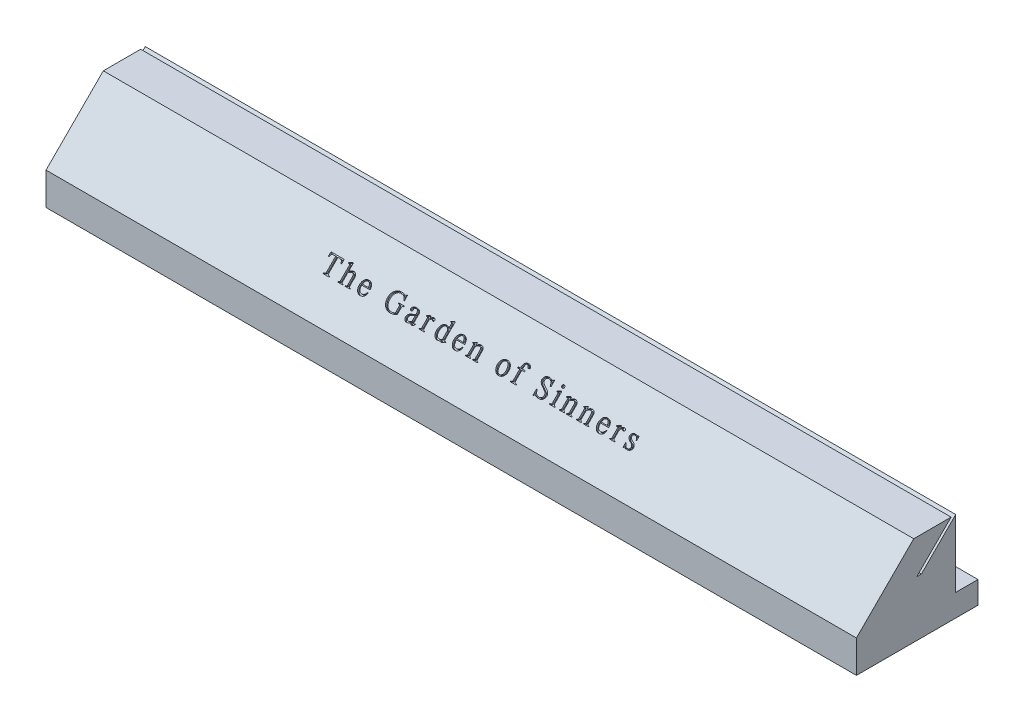
SolidWorks part; units mm, degrees
ref_plane "정면" through (0, 0, 0) normal (0, 0, 1) x (1, 0, 0)
ref_plane "윗면" through (0, 0, 0) normal (0, 1, 0) x (1, 0, 0)
ref_plane "우측면" through (0, 0, 0) normal (1, 0, 0) x (0, 0, -1)
sketch "스케치1" plane through (0, 0, 0) normal (1, 0, 0) x (0, 0, -1)
  line L0 (0, 0) -> (0, 8)
  line L1 (0, 8) -> (14.1421, 22.1421)
  line L2 (14.1421, 22.1421) -> (23.3686, 22.1421)
  line L3 (14.8833, 13.6569) -> (16.0147, 13.6569)
  line L4 (24.5, 22.1421) -> (16.0147, 13.6569)
  line L5 (23.3686, 22.1421) -> (14.8833, 13.6569)
  line L6 (0, 0) -> (30, 0)
  line L7 (30, 0) -> (30, 5.5)
  line L8 (30, 5.5) -> (24.5, 5.5)
  line L9 (24.5, 5.5) -> (24.5, 22.1421)
  dimension "D7" = 12
  dimension "D1" = 30
  dimension "D2" = 8
  dimension "D3" = 20
  dimension "D4" = 135
  dimension "D5" = 45
  dimension "D6" = 0.8
  dimension "D8" = 5.5
  dimension "D9" = 5.5
extrude "보스-돌출1" add sketch "스케치1" along normal blind 200
sketch "스케치2" plane through (0, 4, 4) normal (0, 0.7071, 0.7071) x (1, 0, 0)
  line L0 (0, 14.182) -> (200, 14.182) construction
  text T0 "The Garden of Sinners" font "Yoon 윤명조 740" height 4
extrude "컷-돌출1" cut sketch "스케치2" against normal blind 0.5
